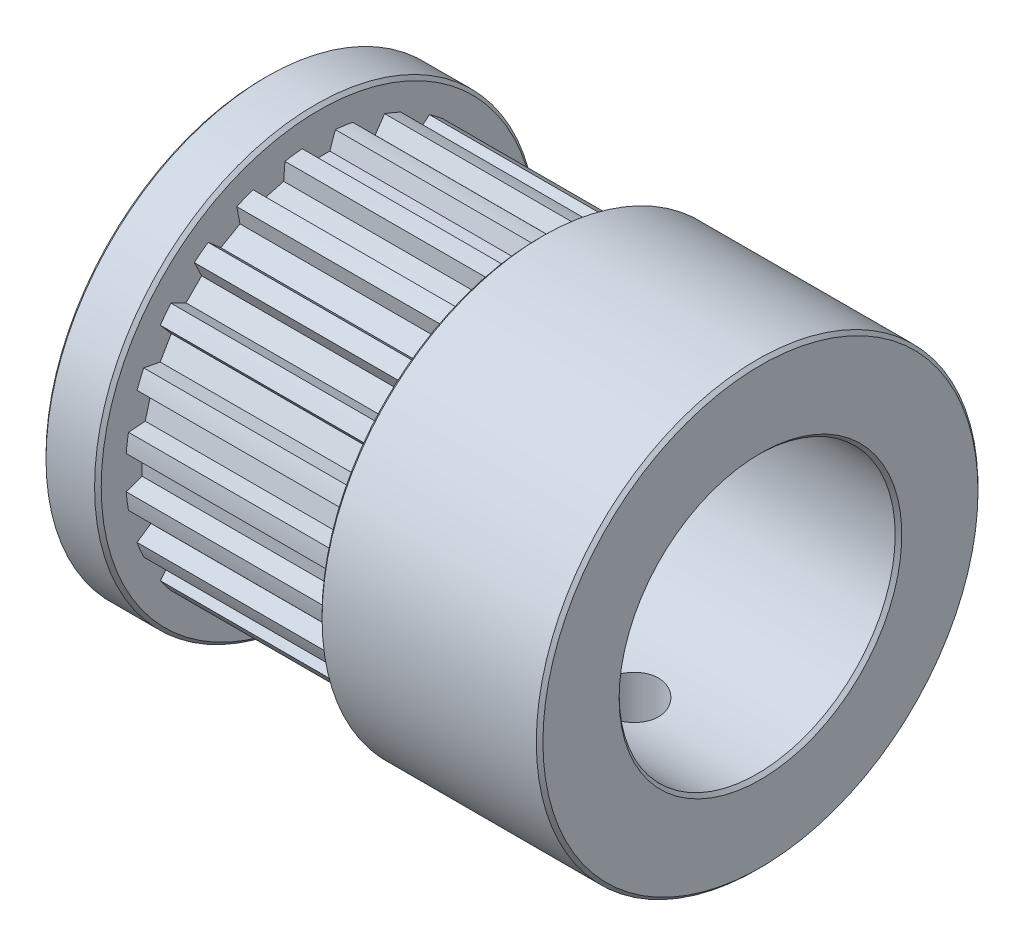
SolidWorks part; units mm, degrees
material "Полиамид П-12Б-20 ТУ 6-05-988-87"
ref_plane "Спереди" through (0, 0, 0) normal (0, 0, 1) x (1, 0, 0)
ref_plane "Сверху" through (0, 0, 0) normal (0, 1, 0) x (1, 0, 0)
ref_plane "Справа" through (0, 0, 0) normal (1, 0, 0) x (0, 0, -1)
ref_axis "ОсьX" through (-88.99, 0, 0) along (1, 0, 0)
ref_axis "ОсьZ" through (0, 55, 0) along (0, -1, 0)
ref_axis "ОсьY" through (0, 0, -88.99) along (0, 0, 1)
sketch "Эскиз1" plane through (0, 0, 0) normal (0, 0, 1) x (1, 0, 0)
  line L0 (-33.311, 0) -> (19.5594, 0) construction
  line L1 (0, 12.5) -> (0, 20)
  line L2 (0, 20) -> (-20, 20)
  line L3 (-20, 20) -> (-20, 17.5)
  line L4 (-20, 17.5) -> (-40, 17.5)
  line L5 (-40, 17.5) -> (-40, 20)
  line L6 (-40, 20) -> (-45, 20)
  line L7 (-45, 20) -> (-45, 12.5)
  line L8 (-45, 12.5) -> (0, 12.5)
  dimension "D1" = 25
  dimension "D2" = 35
  dimension "D3" = 20
  dimension "D4" = 20
  dimension "D5" = 5
  dimension "D6" = 40
revolve "Повернуть1" add sketch "Эскиз1" angle 360 mid plane about L0
sketch "Эскиз2" plane through (0, 0, 0) normal (0, 1, 0) x (1, 0, 0)
  line L0 (0, -20) -> (0, 20) construction
  circle A0 centre (-12, 0) radius 2.75
  dimension "D1" = 5.5
  dimension "D2" = 12
extrude "Вырез-Вытянуть1" cut sketch "Эскиз2" against normal through all
sketch "Эскиз3" plane through (-20, 0, 0) normal (-1, 0, 0) x (0, 0, 1)
  line L0 (-1.5, 17.4356) -> (-1, 16)
  line L1 (-1, 16) -> (1, 16)
  line L2 (1, 16) -> (1.5, 17.4356)
  circle A0 centre (0, 0) radius 17.5 construction
  arc A1 (1.5, 17.4356) -> (-1.5, 17.4356) centre (0, 0) ccw
  point P7 (0, 16)
  dimension "D1" = 1.5
  dimension "D2" = 2
  dimension "D3" = 3
extrude "Вырез-Вытянуть2" cut sketch "Эскиз3" along normal up to surface (20 mm away) up to face at (-40, 0, 20)
pattern_circular "Круговой массив1" count 24 over 360 about axis through (-33.311, 0, 0) along (-1, 0, 0) of "Вырез-Вытянуть2" reverse direction yes
chamfer "Фаска1" distance 0.3 angle 45 6 edges at (-45, 0, 12.5) (-45, 0, 20) (-40, 0, 20) (-20, 0, 20) (0, 0, 20) (0, 0, 12.5)
